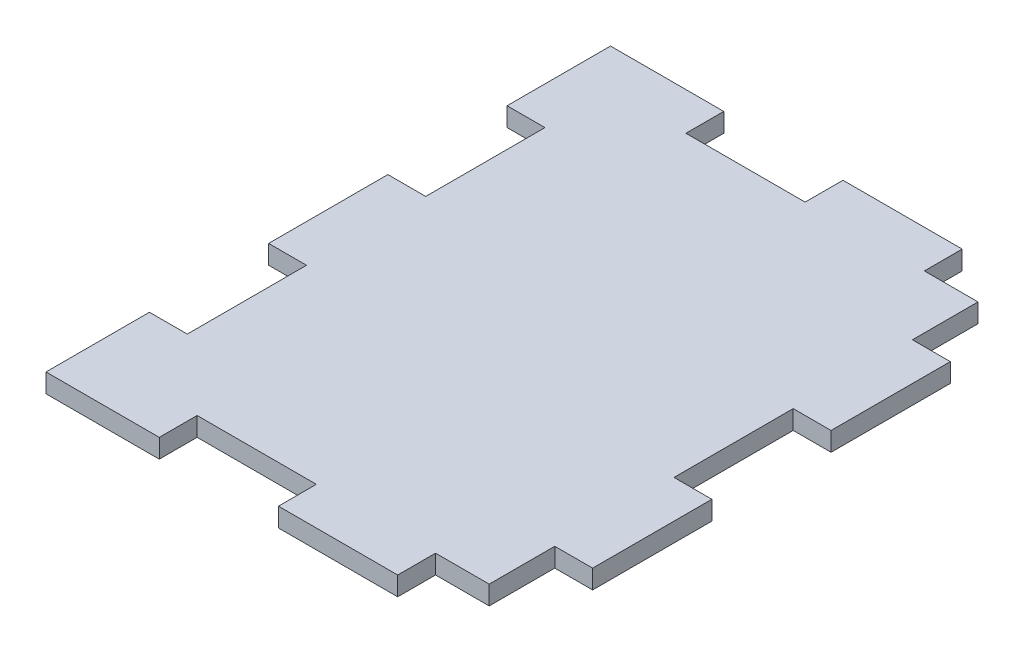
SolidWorks part; units mm, degrees
ref_plane "Front Plane" through (0, 0, 0) normal (0, 0, 1) x (1, 0, 0)
ref_plane "Top Plane" through (0, 0, 0) normal (0, 1, 0) x (1, 0, 0)
ref_plane "Right Plane" through (0, 0, 0) normal (1, 0, 0) x (0, 0, -1)
sketch "Sketch1" plane through (0, 0, 0) normal (0, 1, 0) x (1, 0, 0)
  line L1 (0, 0) -> (37.175, 0)
  line L2 (0, 0) -> (0, 47.35)
  line L3 (0, 47.35) -> (37.175, 47.35)
  line L4 (37.175, 0) -> (37.175, 47.35)
  dimension "D1" = 37.175
  dimension "D2" = 47.35
extrude "Boss-Extrude1" add sketch "Sketch1" along normal blind 1.5875
sketch "Sketch2" plane through (0, 1.5875, 0) normal (0, 1, 0) x (1, 0, 0)
  line L0 (0, 47.35) -> (0, 0) construction
  line L1 (3.175, 38.675) -> (0, 38.675)
  line L2 (3.175, 38.675) -> (3.175, 28.675)
  line L3 (3.175, 28.675) -> (0, 28.675)
  line L4 (0, 38.675) -> (0, 28.675)
  line L5 (37.175, 0) -> (37.175, 47.35) construction
  line L6 (3.175, 18.675) -> (0, 18.675)
  line L7 (3.175, 18.675) -> (3.175, 8.675)
  line L8 (3.175, 8.675) -> (0, 8.675)
  line L9 (0, 18.675) -> (0, 8.675)
  line L10 (34, 18.675) -> (37.175, 18.675)
  line L11 (34, 38.675) -> (34, 44.175)
  line L12 (34, 8.675) -> (37.175, 8.675)
  line L13 (37.175, 38.675) -> (37.175, 47.35)
  line L14 (37.175, 47.35) -> (0, 47.35) construction
  line L15 (34, 28.675) -> (37.175, 28.675)
  line L16 (37.175, 28.675) -> (37.175, 18.675)
  line L17 (34, 38.675) -> (37.175, 38.675)
  line L18 (34, 28.675) -> (34, 18.675)
  line L19 (29.5, 44.175) -> (34, 44.175)
  line L20 (29.5, 44.175) -> (29.5, 47.35)
  line L21 (29.5, 47.35) -> (37.175, 47.35)
  line L23 (19.5, 44.175) -> (9.5, 44.175)
  line L24 (19.5, 44.175) -> (19.5, 47.35)
  line L25 (19.5, 47.35) -> (9.5, 47.35)
  line L26 (9.5, 44.175) -> (9.5, 47.35)
  line L27 (29.5, 3.175) -> (37.175, 3.175)
  line L28 (29.5, 3.175) -> (29.5, 0)
  line L29 (29.5, 0) -> (37.175, 0)
  line L30 (37.175, 3.175) -> (37.175, 0)
  line L31 (19.5, 3.175) -> (9.5, 3.175)
  line L32 (19.5, 3.175) -> (19.5, 0)
  line L33 (19.5, 0) -> (9.5, 0)
  line L34 (9.5, 3.175) -> (9.5, 0)
  line L35 (37.175, 47.35) -> (0, 47.35) construction
  line L36 (0, 47.35) -> (0, 0) construction
  line L37 (37.175, 8.675) -> (37.175, 3.175)
  line L38 (34, 8.675) -> (34, 3.175)
  point P42 (37.175, 46.8752)
  line M28 (0, 47.35) -> (0, 0)
  line M29 (0, 0) -> (37.175, 0)
  line M30 (37.175, 0) -> (37.175, 47.35)
  line M31 (37.175, 47.35) -> (0, 47.35)
  dimension "D1" = 10
  dimension "D2" = 10
  dimension "D3" = 8.675
  dimension "D4" = 41
  dimension "D5" = 9.5
  dimension "D6" = 10
  dimension "D7" = 3.175
  dimension "D8" = 10
extrude "Cut-Extrude1" cut sketch "Sketch2" against normal through all contours L20 L19 L11 L17 M30 M31 | L15 L18 L10 M30 | L27 L28 M29 M30 | L12 L38 L27 M30 | L31 L34 L32 M29 | L8 L7 L6 M28 | L3 L2 L1 M28 | L26 L23 L24 M31 region at (1.5875, 1.5875, -33.675) region at (1.5875, 1.5875, -13.675) region at (14.5, 1.5875, -45.7625) region at (34.2768, 1.5875, -43.9518) region at (14.5, 1.5875, -1.5875) region at (33.3375, 1.5875, -1.5875) region at (35.5875, 1.5875, -23.675) region at (35.5875, 1.5875, -5.925)
